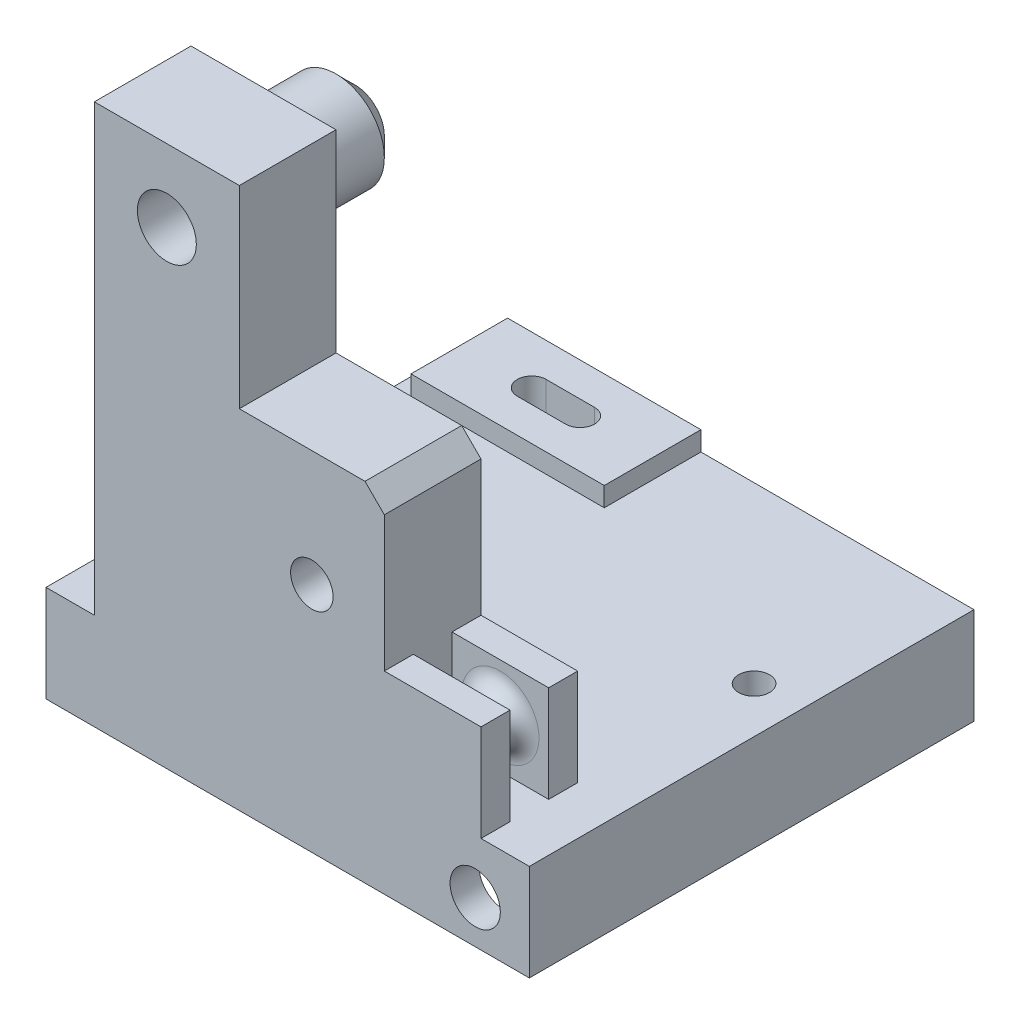
SolidWorks part; units mm, degrees
ref_plane "Front Plane" through (0, 0, 0) normal (0, 0, 1) x (1, 0, 0)
ref_plane "Top Plane" through (0, 0, 0) normal (0, 1, 0) x (1, 0, 0)
ref_plane "Right Plane" through (0, 0, 0) normal (1, 0, 0) x (0, 0, -1)
sketch "Sketch1" plane through (0, 0, 0) normal (0, 0, 1) x (1, 0, 0)
  line L0 (-15, 0) -> (-15, 46)
  line L1 (-15, 46) -> (0, 46)
  line L2 (0, 46) -> (0, 26)
  line L5 (0, 26) -> (15, 26)
  line L6 (15, 26) -> (15, 0)
  line L12 (-15, 0) -> (15, 0)
  circle A0 centre (-7.5, 38.5) radius 3.05
  circle A1 centre (7.5, 14) radius 2.2
  point P8 (0, 0)
  point P12 (-7.5, 46)
  point P16 (7.5, 26)
  dimension "D7" = 6.1
  dimension "D9" = 4.4
  dimension "D1" = 46
  dimension "D2" = 15
  dimension "D3" = 30
  dimension "D6" = 20
  dimension "D8" = 7.5
  dimension "D10" = 12
extrude "Boss-Extrude1" add sketch "Sketch1" along normal blind 6 and the other way blind 4
sketch "Sketch2" plane through (15, 0, 0) normal (1, 0, 0) x (0, 0, -1)
  line L0 (-6, 0) -> (4, 0) construction
  line L1 (-6, 0) -> (-6, 26) construction
  circle A0 centre (-1, 5) radius 2.5
  dimension "D1" = 5
  dimension "D2" = 5
  dimension "D3" = 5
extrude "Boss-Extrude2" [suppressed] add sketch "Sketch2" along normal blind 6
sketch "Sketch3" [suppressed] plane through (21, 0, 0) normal (1, 0, 0) x (0, 0, -1)
  circle A0 centre (-5, 5) radius 4.5
  circle A1 centre (-5, 5) radius 2.5
  circle A2 centre (-5, 5) radius 2.5 construction
  dimension "D1" = 0
  dimension "D2" = 2
extrude "Boss-Extrude3" [suppressed] add sketch "Sketch3" along normal blind 2
ref_plane "Plane1" through (0, 0, -4) normal (0, 0, -1) x (-1, 0, 0)
sketch "Sketch4" plane through (0, 0, -4) normal (0, 0, -1) x (-1, 0, 0)
  line L0 (-15, 0) -> (-15, 10)
  line L1 (-15, 0) -> (-25, 0)
  line L2 (-15, 10) -> (-25, 10)
  line L3 (-25, 0) -> (-25, 10)
  line L4 (-15, 0) -> (-15, 26) construction
  dimension "D1" = 10
  dimension "D2" = 10
extrude "Boss-Extrude4" add sketch "Sketch4" against normal blind 10
sketch "Sketch5" plane through (25, 0, 0) normal (1, 0, 0) x (0, 0, -1)
  line L0 (-3, 10) -> (1, 10)
  line L1 (-3, 10) -> (-3, 0)
  line L2 (1, 10) -> (1, 0)
  line L3 (-3, 0) -> (1, 0)
  line L4 (-6, 10) -> (4, 10) construction
  line L5 (-6, 0) -> (4, 0) construction
  line L7 (-6, 10) -> (4, 10) construction
  point P8 (-1, 10)
  dimension "D1" = 4
extrude "Cut-Extrude1" cut sketch "Sketch5" against normal up to surface (10 mm away) up to face at (15, 18, 1)
sketch "Sketch6" plane through (0, 0, -1) normal (0, 0, 1) x (1, 0, 0)
  line L0 (25, 10) -> (25, 0) construction
  line L1 (15, 10) -> (25, 10) construction
  circle A0 centre (20, 5) radius 2
  dimension "D1" = 4
  dimension "D2" = 5
  dimension "D3" = 5
extrude "Boss-Extrude5" add sketch "Sketch6" along normal up to next
fillet "Fillet1" radius 2 2 edges at (20, 3, 3) (20, 7, -1)
chamfer "Chamfer1" distance 2 angle 45 1 edges at (15, 26, 1)
sketch "Sketch7" plane through (0, 0, 0) normal (0, -1, 0) x (1, 0, 0)
  line L1 (25, 6) -> (-15, 6) construction
  line L2 (25, 6) -> (25, -9.5) construction
  line L3 (25, -9.5) -> (-15, -9.5) construction
  line L4 (-15, 6) -> (-15, -9.5) construction
  line L5 (-15, 6) -> (-15, -4) construction
  line L12 (30, -14.5) -> (-20, -14.5)
  line L24 (-16.5, -4) -> (16.5, -4) construction
  line L32 (30, 11) -> (-20, 11) construction
  line L33 (-20, 11) -> (-20, -14.5) construction
  line L34 (30, 11) -> (30, -14.5) construction
  line L35 (-20, -14.5) -> (-20, 6)
  line L36 (-20, 6) -> (30, 6)
  line L37 (30, 6) -> (30, -14.5)
  line L38 (-15, 6) -> (25, 6) construction
  dimension "D2" = 5.5
  dimension "D1" = 5
extrude "Boss-Extrude6" add sketch "Sketch7" along normal blind 10
sketch "Sketch12" plane through (0, 0, 0) normal (0, 1, 0) x (1, 0, 0)
  line L0 (-15, 4) -> (25, 4) construction
  line L3 (-20, 9) -> (-2.5, 9) construction
  line L4 (-20, -6) -> (-20, 14.5) construction
  line L5 (-10.75, 10.5) -> (-5.75, 10.5)
  line L6 (-10.75, 7.5) -> (-5.75, 7.5)
  circle A2 centre (-8.25, 9) radius 1.5 construction
  arc A3 (-10.75, 10.5) -> (-10.75, 7.5) centre (-10.75, 9) ccw
  arc A4 (-5.75, 10.5) -> (-5.75, 7.5) centre (-5.75, 9) cw
  point P12 (-8.25, 7.5)
  point P13 (-8.25, 10.5)
  point P14 (-11.25, 9)
  dimension "D1" = 3
  dimension "D2" = 3
  dimension "D3" = 17.5
  dimension "D4" = 5
  dimension "D5" = 5
sketch "Sketch13" plane through (0, 0, -14.5) normal (0, 0, -1) x (-1, 0, 0)
  line L1 (-30, 0) -> (20, 0)
  line L2 (-30, 0) -> (-30, -10)
  line L3 (-30, -10) -> (20, -10)
  line L4 (20, 0) -> (20, -10)
extrude "Boss-Extrude9" add sketch "Sketch13" along normal blind 25.5
sketch "Sketch14" plane through (0, 0, 0) normal (0, 1, 0) x (1, 0, 0)
  line L0 (-20, 22) -> (30, 22) construction
  line L3 (30, 40) -> (30, -6) construction
  line L4 (-20, -6) -> (-20, 40) construction
  line L7 (0, 4) -> (-15, 4) construction
  dimension "D1" = 18
ref_plane "Plane2" through (0, 0, -22) normal (0, 0, -1) x (-1, 0, 0)
sketch "Sketch16" plane through (0, -10, 0) normal (0, -1, 0) x (1, 0, 0)
  line L8 (27, -37) -> (27, 3)
  line L9 (27, -37) -> (27, 3)
  line L10 (-17, -37) -> (27, -37)
  line L11 (27, 3) -> (-17, 3)
  line L14 (-17, -37) -> (27, -37)
  line L16 (27, 3) -> (-17, 3)
  line L17 (-17, 3) -> (-17, -37)
  line L18 (-17, 3) -> (-17, -37)
  dimension "D1" = 3
extrude "Cut-Extrude3" cut sketch "Sketch16" against normal blind 7
sketch "Sketch17" plane through (0, 0, 6) normal (0, 0, 1) x (1, 0, 0)
  line L1 (-20, 0) -> (30, 0) construction
  line L2 (30, -10) -> (30, 0) construction
  circle A0 centre (24.4, -5.6) radius 2.6
  dimension "D1" = 5.2
  dimension "D2" = 5.6
  dimension "D3" = 5.6
extrude "Cut-Extrude4" cut sketch "Sketch17" against normal up to surface (3 mm away) up to face at (5, -6.5, 3)
sketch "Sketch18" plane through (-20, 0, 0) normal (-1, 0, 0) x (0, 0, 1)
  line L1 (-9, -10) -> (-11, -10)
  line L2 (-9, -10) -> (-9, 0)
  line L3 (-9, 0) -> (-11, 0)
  line L4 (-11, -10) -> (-11, 0)
  line L6 (-40, -10) -> (-40, 0) construction
  line L7 (6, 0) -> (-40, 0) construction
  line L8 (6, -10) -> (-40, -10) construction
  dimension "D1" = 2
  dimension "D2" = 29
extrude "Boss-Extrude11" add sketch "Sketch18" along normal blind 5
fillet "Fillet2" radius 5 1 edges at (-20, -5, -11)
ref_plane "Plane3" through (-7.5, 0, 0) normal (1, 0, 0) x (0, 0, -1)
sketch "Sketch19" plane through (-7.5, 0, 0) normal (-1, 0, 0) x (0, 0, 1)
  line L0 (-4, 38.5) -> (-14, 38.5)
  line L1 (-4, 46) -> (-4, 0) construction
  line L2 (-11.5, 43.5) -> (-4, 43.5)
  line L3 (-4, 43.5) -> (-4, 38.5)
  line L4 (-4, 46) -> (6, 46) construction
  line L5 (-14, 38.5) -> (-14, 41)
  line L6 (-11.5, 43.5) -> (-14, 41)
  dimension "D2" = 135
  dimension "D1" = 7.5
  dimension "D3" = 10
  dimension "D4" = 5
  dimension "D5" = 2.5
revolve "Revolve1" add sketch "Sketch19" angle 360 about L0
sketch "Sketch20" plane through (0, 0, -4) normal (0, 0, 1) x (1, 0, 0)
  circle A1 centre (-7.5, 38.5) radius 3.05
  circle A2 centre (-7.5, 38.5) radius 3.05
  dimension "D1" = 0
extrude "Cut-Extrude5" cut sketch "Sketch20" against normal up to next
fillet "Fillet5" radius 1.5 1 edges at (-12.5, 38.5, -4)
extrude "Cut-Extrude6" cut sketch "Sketch12" against normal blind 3 contours A4 L6 A3 L5
sketch "Sketch22" plane through (0, 0, 0) normal (0, 1, 0) x (1, 0, 0)
  line L0 (16.5, 4) -> (-16.5, 4) construction
  line L1 (-18.25, 14) -> (1.75, 14)
  line L2 (-18.25, 14) -> (-18.25, 4)
  line L3 (-18.25, 4) -> (1.75, 4)
  line L4 (1.75, 14) -> (1.75, 4)
  line L5 (-8.25, 4) -> (-8.25, 14) construction
  line L6 (-10.75, 7.5) -> (-5.75, 7.5) construction
  line L7 (-10.75, 10.5) -> (-5.75, 10.5) construction
  line L8 (-10.75, 7.5) -> (-5.75, 7.5)
  line L9 (-10.75, 10.5) -> (-5.75, 10.5)
  line L10 (5.5, 22) -> (-5.5, 22) construction
  line L11 (-10.75, 36.5) -> (-5.75, 36.5)
  line L12 (-10.75, 33.5) -> (-5.75, 33.5)
  line L13 (-18.25, 40) -> (1.75, 40)
  line L14 (1.75, 30) -> (1.75, 40)
  line L15 (-18.25, 30) -> (1.75, 30)
  line L16 (-18.25, 30) -> (-18.25, 40)
  arc A0 (-10.75, 33.5) -> (-10.75, 36.5) centre (-10.75, 35) cw
  arc A2 (-5.75, 7.5) -> (-5.75, 10.5) centre (-5.75, 9) ccw construction
  arc A3 (-10.75, 10.5) -> (-10.75, 7.5) centre (-10.75, 9) ccw construction
  arc A4 (-5.75, 7.5) -> (-5.75, 10.5) centre (-5.75, 9) ccw
  arc A5 (-10.75, 10.5) -> (-10.75, 7.5) centre (-10.75, 9) ccw
  arc A6 (-5.75, 36.5) -> (-5.75, 33.5) centre (-5.75, 35) cw
  point P15 (-8.25, 10.5)
  dimension "D1" = 20
  dimension "D2" = 10
extrude "Boss-Extrude12" add sketch "Sketch22" along normal blind 2
mirror "Mirror2" [suppressed] about plane through (0, 0, -22) normal (0, 0, -1)
sketch "Sketch23" plane through (0, 0, 0) normal (0, 1, 0) x (1, 0, 0)
  line L0 (-20, 22) -> (30, 22) construction
  line L1 (30, 40) -> (30, -6) construction
  circle A0 centre (25.25, 22) radius 1.6
  dimension "D1" = 3.2
  dimension "D2" = 4.75
extrude "Cut-Extrude7" cut sketch "Sketch23" against normal up to next
sketch "Sketch24" plane through (0, 0, 0) normal (0, 1, 0) x (1, 0, 0)
  line L2 (-10.75, 33.5) -> (-5.75, 33.5)
  line L6 (-10.75, 33.5) -> (-5.75, 33.5)
  line L7 (-5.75, 36.5) -> (-10.75, 36.5)
  line L8 (-5.75, 36.5) -> (-10.75, 36.5)
  arc A1 (-10.75, 36.5) -> (-10.75, 33.5) centre (-10.75, 35) ccw
  arc A6 (-10.75, 36.5) -> (-10.75, 33.5) centre (-10.75, 35) ccw
  arc A7 (-5.75, 33.5) -> (-5.75, 36.5) centre (-5.75, 35) ccw
  arc A8 (-5.75, 33.5) -> (-5.75, 36.5) centre (-5.75, 35) ccw
  dimension "D1" = 0
extrude "Cut-Extrude8" cut sketch "Sketch24" against normal through all
